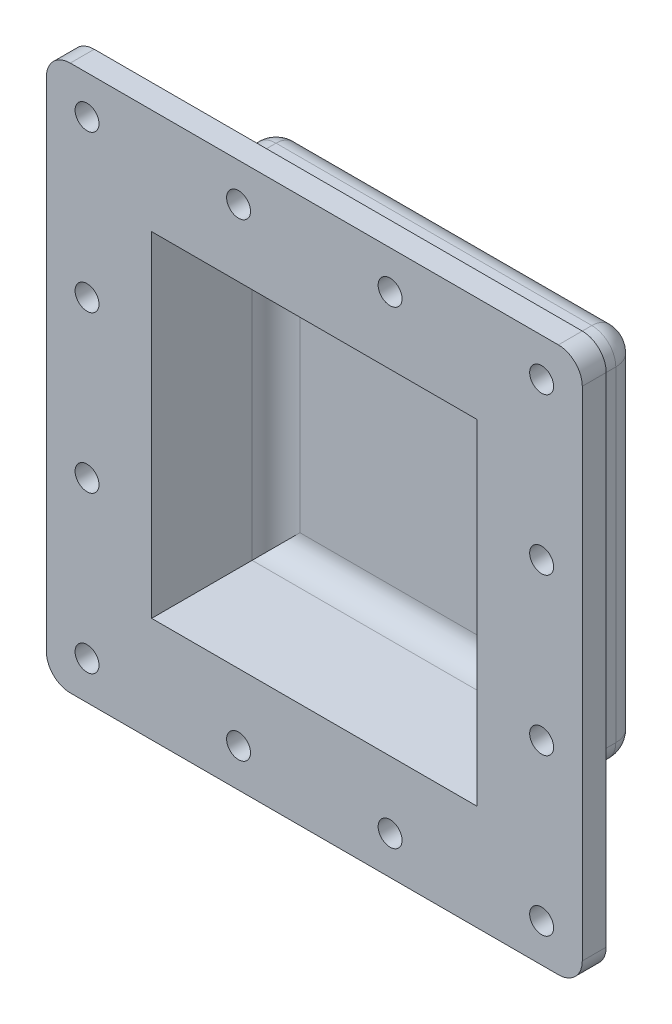
SolidWorks part; units mm, degrees
ref_plane "Front Plane" through (0, 0, 0) normal (0, 0, 1) x (1, 0, 0)
ref_plane "Top Plane" through (0, 0, 0) normal (0, 1, 0) x (1, 0, 0)
ref_plane "Right Plane" through (0, 0, 0) normal (1, 0, 0) x (0, 0, -1)
sketch "Sketch1" plane through (0, 0, 0) normal (0, 0, 1) x (1, 0, 0)
  line L1 (-19, 19.5) -> (19, 19.5)
  line L2 (-19, 19.5) -> (-19, -19.5)
  line L3 (-19, -19.5) -> (19, -19.5)
  line L4 (19, 19.5) -> (19, -19.5)
  line L5 (-19, 19.5) -> (19, -19.5) construction
  line L6 (-19, -19.5) -> (19, 19.5) construction
  point P0 (0, 0)
  dimension "D1" = 38
  dimension "D2" = 39
extrude "Boss-Extrude1" add sketch "Sketch1" along normal blind 12.5
shell "Shell1" thickness 2 removed face at (0, 0, 12.5)
sketch "Sketch2" plane through (0, 0, 12.5) normal (0, 0, 1) x (1, 0, 0)
  line L0 (-19, 19.5) -> (-19, -19.5) construction
  line L1 (-28, 28.5) -> (28, 28.5)
  line L2 (-28, 28.5) -> (-28, -28.5)
  line L3 (-28, -28.5) -> (28, -28.5)
  line L4 (28, 28.5) -> (28, -28.5)
  line L5 (-28, 28.5) -> (28, -28.5) construction
  line L6 (-28, -28.5) -> (28, 28.5) construction
  line L7 (-19, 19.5) -> (19, 19.5) construction
  line L8 (17, -17.5) -> (17, 17.5) construction
  line L9 (-17, -17.5) -> (17, -17.5)
  line L10 (-17, -17.5) -> (-17, 17.5)
  line L11 (-17, 17.5) -> (17, 17.5)
  line L12 (17, -17.5) -> (17, 17.5)
  line L13 (-17, -17.5) -> (17, 17.5) construction
  line L14 (-17, 17.5) -> (17, -17.5) construction
  line L15 (17, -17.5) -> (17, 17.5) construction
  point P0 (0, 0)
  point P10 (0, 0)
  dimension "D1" = 9
  dimension "D2" = 9
extrude "Boss-Extrude2" add sketch "Sketch2" along normal blind 2.5
fillet "Fillet1" radius 2.5 4 edges at (-28, -28.5, 13.75) (28, -28.5, 13.75) (28, 28.5, 13.75) (-28, 28.5, 13.75)
fillet "Fillet2" radius 2.5 12 edges at (0, -17.5, 2) (17, 0, 2) (-17, 0, 2) (0, 17.5, 2) (0, -19.5, 0) (19, 0, 0) (0, 19.5, 0) (-19, 0, 0) (19, -19.5, 6.25) (19, 19.5, 6.25) (-19, -19.5, 6.25) (-19, 19.5, 6.25)
sketch "Sketch3" plane through (0, 0, 2) normal (0, 0, 1) x (1, 0, 0)
  line L1 (-7.5, 14) -> (7.5, 14)
  line L2 (-7.5, 14) -> (-7.5, 6)
  line L3 (-7.5, 6) -> (7.5, 6)
  line L4 (7.5, 14) -> (7.5, 6)
  line L5 (-7.5, 14) -> (7.5, 6) construction
  line L6 (-7.5, 6) -> (7.5, 14) construction
  point P0 (0, 10)
  dimension "D1" = 8
  dimension "D2" = 15
  dimension "D3" = 10
extrude "Cut-Extrude1" cut sketch "Sketch3" against normal through all
sketch "Sketch4" plane through (0, 0, 15) normal (0, 0, 1) x (1, 0, 0)
  line L1 (-19, 19.5) -> (-19, -19.5) construction
  line L2 (-19, 19.5) -> (19, 19.5) construction
  line L3 (-23.75, 24.5) -> (23.75, 24.5) construction
  line L10 (-23.75, 24.5) -> (-23.75, -24.5) construction
  line L11 (-23.75, -24.5) -> (23.75, -24.5) construction
  line L18 (23.75, 24.5) -> (23.75, -24.5) construction
  line L19 (-23.75, 24.5) -> (23.75, -24.5) construction
  line L20 (-23.75, -24.5) -> (23.75, 24.5) construction
  circle A21 centre (-23.75, 24.5) radius 1.25
  circle A25 centre (-7.9167, 24.5) radius 1.25
  circle A26 centre (7.9167, 24.5) radius 1.25
  circle A27 centre (23.75, 24.5) radius 1.25
  circle A30 centre (23.75, 8.1667) radius 1.25
  circle A33 centre (23.75, -8.1667) radius 1.25
  circle A34 centre (-7.9167, -24.5) radius 1.25
  circle A35 centre (7.9167, -24.5) radius 1.25
  circle A36 centre (23.75, -24.5) radius 1.25
  circle A37 centre (-23.75, 8.1667) radius 1.25
  circle A38 centre (-23.75, -8.1667) radius 1.25
  circle A39 centre (-23.75, -24.5) radius 1.25
  circle A40 centre (-7.9167, 8.1667) radius 1.25 [skipped]
  circle A41 centre (7.9167, 8.1667) radius 1.25 [skipped]
  circle A42 centre (-7.9167, -8.1667) radius 1.25 [skipped]
  circle A43 centre (7.9167, -8.1667) radius 1.25 [skipped]
  point P0 (0, 0)
  dimension "D1" = 4.75
  dimension "D3" = 2.5
  dimension "D2" = 5
  dimension "D5" = 4
  dimension "D4" = 4
extrude "Cut-Extrude2" cut sketch "Sketch4" against normal up to surface (2.5 mm away) up to face at (0, 0, 12.5)
equation "\"case_width\"=38.00"
equation "\"D1@Sketch1\"=\"case_width\""
